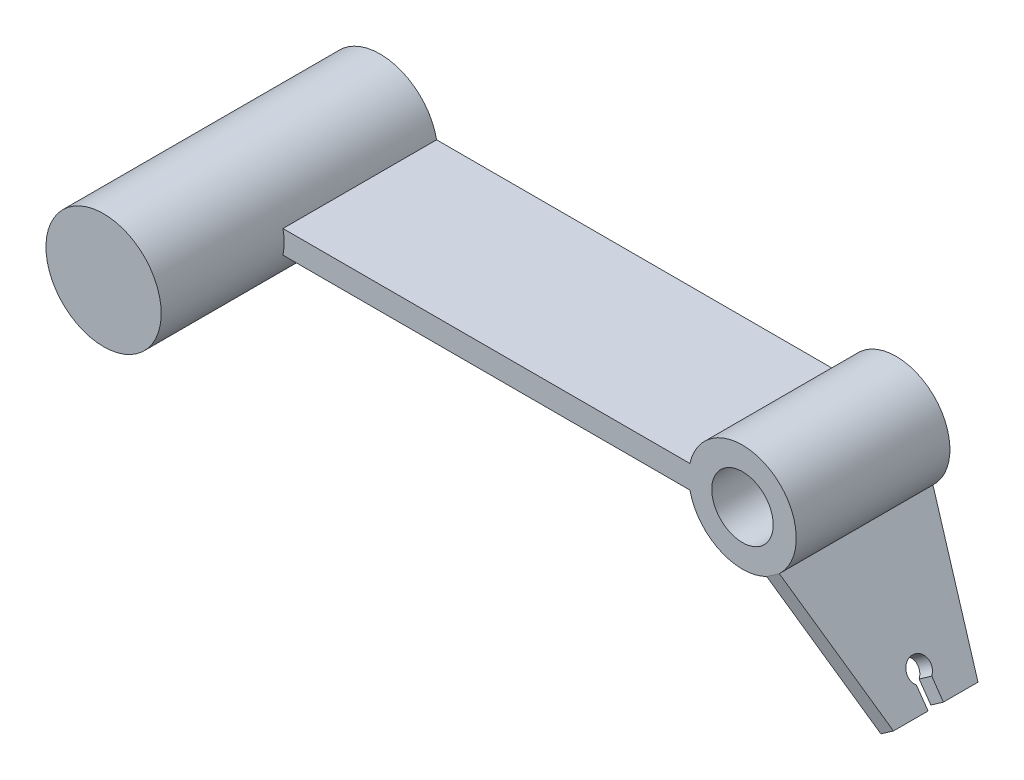
SolidWorks part; units mm, degrees
ref_plane "Front Plane" through (0, 0, 0) normal (0, 0, 1) x (1, 0, 0)
ref_plane "Top Plane" through (0, 0, 0) normal (0, 1, 0) x (1, 0, 0)
ref_plane "Right Plane" through (0, 0, 0) normal (1, 0, 0) x (0, 0, -1)
sketch "Sketch2" plane through (0, 0, 0) normal (0, 0, 1) x (1, 0, 0)
  line L0 (0, 0) -> (-7, 0) construction
  line L1 (-7, 0) -> (-37, 0) construction
  line L3 (-67.1626, 1.5) -> (-6.8374, 1.5)
  line L4 (-67.1626, 1.5) -> (-67.1626, -1.5)
  line L5 (-67.1626, -1.5) -> (-6.8374, -1.5)
  line L7 (-67.1626, 1.5) -> (-6.8374, -1.5) construction
  line L8 (-67.1626, -1.5) -> (-6.8374, 1.5) construction
  circle A0 centre (0, 0) radius 4
  arc A1 (-6.8374, -1.5) -> (-6.8374, 1.5) centre (0, 0) ccw
  dimension "D1" = 8
  dimension "D2" = 3
  dimension "D3" = 3
  dimension "D4" = 30
  dimension "D5" = 7
extrude "Boss-Extrude1" add sketch "Sketch2" along normal blind 20
sketch "Sketch3" plane through (0, 0, 20) normal (0, 0, 1) x (1, 0, 0)
  line L0 (-67.1626, 1.5) -> (-67.1626, -1.5) construction
  circle A0 centre (-67.1626, 0) radius 7.5
  dimension "D1" = 15
extrude "Boss-Extrude2" add sketch "Sketch3" against normal through all and the other way blind 16
sketch "Sketch4" plane through (0, 0, 20) normal (0, 0, 1) x (1, 0, 0)
  line L0 (0, 0) -> (14.3394, -20.4788) construction
  line L2 (-59.8141, -1.5) -> (-6.8374, -1.5) construction
  line L3 (15.1586, -19.9052) -> (13.5203, -21.0524)
  line L4 (13.5203, -21.0524) -> (3.1547, -6.2488)
  line L5 (15.1586, -19.9052) -> (4.793, -5.1017)
  arc A0 (3.1547, -6.2488) -> (4.793, -5.1017) centre (0, 0) ccw
  arc A1 (-6.8374, -1.5) -> (-6.8374, 1.5) centre (0, 0) ccw construction
  dimension "D1" = 55
  dimension "D2" = 2
  dimension "D3" = 25
extrude "Boss-Extrude3" add sketch "Sketch4" against normal up to surface (20 mm away) up to face at (-33.5785, 0, 0)
sketch "Sketch5" plane through (0.8192, 0.5736, 0) normal (0.8192, 0.5736, 0) x (0, 0, -1)
  line L0 (-10, -6.9282) -> (-10, -21.2282) construction
  line L1 (0, -6.9282) -> (-20, -6.9282) construction
  line L2 (-11, -22.3462) -> (-11, -25)
  line L3 (0, -25) -> (-20, -25) construction
  line L4 (-9, -22.3462) -> (-9, -25)
  line L5 (-11, -25) -> (-9, -25)
  arc A0 (-9, -22.3462) -> (-11, -22.3462) centre (-10, -21.2282) ccw
  dimension "D1" = 2
  dimension "D2" = 3
  dimension "D3" = 1
  dimension "D4" = 14.3
extrude "Cut-Extrude1" cut sketch "Sketch5" against normal up to surface (2 mm away) contours A0 L2 L5 L4 up to face at (8.3375, -13.6506, 10)
sketch "Sketch6" plane through (0.8192, 0.5736, 0) normal (0.8192, 0.5736, 0) x (0, 0, -1)
  line L0 (-20, -6.9282) -> (-15.5, -25)
  line L1 (-11, -25) -> (-20, -25) construction
  line L2 (-15.5, -25) -> (-21.3798, -25)
  line L3 (-21.3798, -25) -> (-21.3798, -6.6211)
  line L4 (-21.3798, -6.6211) -> (-20, -6.9282)
  line L5 (0, -6.9282) -> (1.4141, -6.9282)
  line L6 (1.4141, -6.9282) -> (1.4141, -25)
  line L7 (1.4141, -25) -> (-4.5, -25)
  line L8 (0, -25) -> (-9, -25) construction
  line L9 (-4.5, -25) -> (0, -6.9282)
extrude "Cut-Extrude2" cut sketch "Sketch6" against normal up to next
sketch "Sketch7" plane through (0, 0, 9) normal (0, 0, 1) x (1, 0, 0)
  line L0 (-25.2484, -1.5) -> (8.3375, -13.6506)
  line L1 (-59.8141, -1.5) -> (-6.8374, -1.5) construction
  line L2 (13.5203, -21.0524) -> (3.1547, -6.2488) construction
  line L3 (8.3375, -13.6506) -> (3.1547, -6.2488)
  line L4 (3.1547, -6.2488) -> (-6.8374, -1.5)
  line L5 (-6.8374, -1.5) -> (-25.2484, -1.5)
  line L6 (0, 0) -> (-3.402, -9.4035) construction
  dimension "D1" = 10
extrude "Boss-Extrude4" add sketch "Sketch7" along normal blind 2
